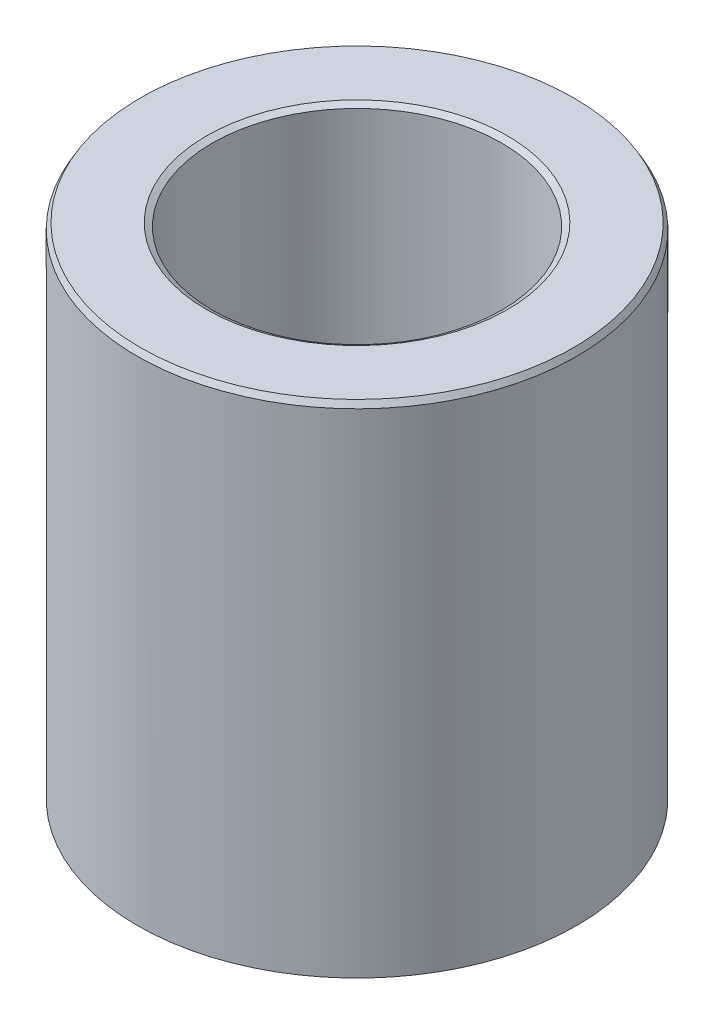
SolidWorks part; units mm, degrees
ref_plane "Front Plane" through (0, 0, 0) normal (0, 0, 1) x (1, 0, 0)
ref_plane "Top Plane" through (0, 0, 0) normal (0, 1, 0) x (1, 0, 0)
ref_plane "Right Plane" through (0, 0, 0) normal (1, 0, 0) x (0, 0, -1)
sketch "Sketch1" plane through (0, 0, 0) normal (0, 1, 0) x (1, 0, 0)
  circle A0 centre (0, 0) radius 45
  dimension "SLEEVE_OD" = 90
extrude "Boss-Extrude1" add sketch "Sketch1" along normal blind 102.8067
sketch "Sketch2" plane through (0, 0, 0) normal (0, 1, 0) x (1, 0, 0)
  circle A0 centre (0, 0) radius 29.6285
  dimension "BORE_D" = 59.257
extrude "Cut-Extrude1" cut sketch "Sketch2" along normal through all
chamfer "Chamfer1" distance 1.1835 angle 30 4 edges at (0, 102.8067, 29.6285) (0, 0, 29.6285) (0, 0, 45) (0, 102.8067, 45) first distance on face at (0, 102.8067, 29.6285) first distance on face at (0, 0, 29.6285) first distance on face at (0, 102.8067, 45)
